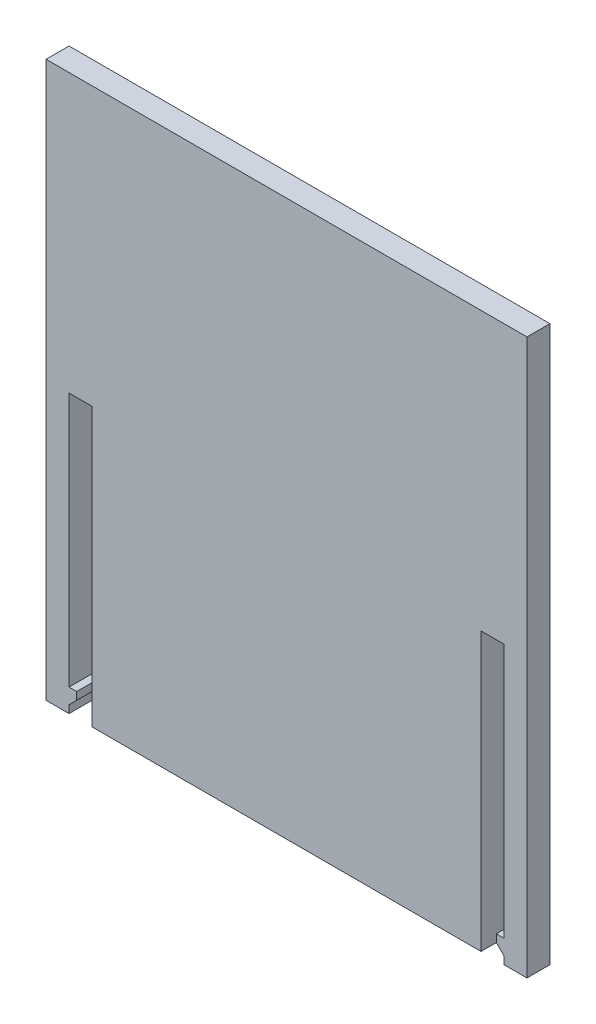
SolidWorks part; units mm, degrees
ref_plane "Front Plane" through (0, 0, 0) normal (0, 0, 1) x (1, 0, 0)
ref_plane "Top Plane" through (0, 0, 0) normal (0, 1, 0) x (1, 0, 0)
ref_plane "Right Plane" through (0, 0, 0) normal (1, 0, 0) x (0, 0, -1)
sketch "Sketch1" plane through (0, 0, 0) normal (0, 0, 1) x (1, 0, 0)
  line L37 (50.8, -10.8558) -> (50.8, -13.8558) construction
  line L38 (50.8, -13.8558) -> (53.8, -13.8558) construction
  line L39 (53.8, -13.8558) -> (53.8, -10.8558) construction
  line L41 (53.8, -10.8558) -> (50.8, -10.8558) construction
  line L42 (-3, -10.8558) -> (-3, -13.8558) construction
  line L43 (-3, -13.8558) -> (0, -13.8558) construction
  line L44 (0, -13.8558) -> (0, -10.8558) construction
  line L45 (0, -10.8558) -> (-3, -10.8558) construction
  line L46 (50.8, 58.6442) -> (50.8, 22.3942) construction
  line L47 (50.8, 22.3942) -> (53.8, 22.3942) construction
  line L48 (53.8, 22.3942) -> (53.8, 58.6442) construction
  line L49 (53.8, 58.6442) -> (50.8, 58.6442) construction
  line L50 (-3, 58.6442) -> (-3, 22.3942) construction
  line L51 (-3, 22.3942) -> (0, 22.3942) construction
  line L52 (0, 22.3942) -> (0, 58.6442) construction
  line L53 (0, 58.6442) -> (-3, 58.6442) construction
  line L54 (50.8, -10.8558) -> (50.8, -13.8558) construction
  line L55 (50.8, -13.8558) -> (53.8, -13.8558) construction
  line L56 (53.8, -13.8558) -> (53.8, -10.8558) construction
  line L57 (53.8, -10.8558) -> (50.8, -10.8558) construction
  line L58 (-3, -10.8558) -> (-3, -13.8558) construction
  line L59 (-3, -13.8558) -> (0, -13.8558) construction
  line L60 (0, -13.8558) -> (0, -10.8558) construction
  line L61 (0, -10.8558) -> (-3, -10.8558) construction
  line L62 (50.8, 58.6442) -> (50.8, 22.3942) construction
  line L63 (50.8, 22.3942) -> (53.8, 22.3942) construction
  line L64 (53.8, 22.3942) -> (53.8, 58.6442) construction
  line L65 (53.8, 58.6442) -> (50.8, 58.6442) construction
  line L66 (-3, 58.6442) -> (-3, 22.3942) construction
  line L67 (-3, 22.3942) -> (0, 22.3942) construction
  line L68 (0, 22.3942) -> (0, 58.6442) construction
  line L69 (0, 58.6442) -> (-3, 58.6442) construction
  line L71 (-6, 58.6442) -> (56.8, 58.6442)
  line L72 (-6, 58.6442) -> (-6, -13.8558)
  line L73 (-6, -13.8558) -> (56.8, -13.8558)
  line L74 (56.8, 58.6442) -> (56.8, -13.8558)
  line L75 (-6, 58.6442) -> (56.8, -13.8558) construction
  line L76 (-6, -13.8558) -> (56.8, 58.6442) construction
  line L77 (-3, 22.3942) -> (0, 22.3942)
  line L78 (-3, 22.3942) -> (-3, -10.8558)
  line L79 (-3, -10.8558) -> (0, -10.8558)
  line L80 (0, 22.3942) -> (0, -10.8558)
  line L81 (50.8, 22.3942) -> (53.8, 22.3942)
  line L82 (50.8, 22.3942) -> (50.8, -10.8558)
  line L83 (50.8, -10.8558) -> (53.8, -10.8558)
  line L84 (53.8, 22.3942) -> (53.8, -10.8558)
  point P2 (25.4, 22.3942)
  dimension "D1" = 3
  dimension "D2" = 3
extrude "Boss-Extrude1" add sketch "Sketch1" along normal blind 3
sketch "Sketch2" plane through (0, 0, 3) normal (0, 0, 1) x (1, 0, 0)
  line L0 (-6, -13.8558) -> (56.8, -13.8558) construction
  line L1 (-3, -10.8558) -> (0, -10.8558)
  line L2 (-3, -10.8558) -> (-3, -13.8558)
  line L3 (-3, -13.8558) -> (0, -13.8558)
  line L4 (0, -10.8558) -> (0, -13.8558)
  line L5 (-3, -10.8558) -> (-2, -10.8558)
  line L6 (-2, -10.8558) -> (-2, -11.8558)
  line L7 (-2, -11.8558) -> (-3, -12.8558)
  line M11 (-6, -13.8558) -> (56.8, -13.8558)
  line M17 (0, -10.8558) -> (-3, -10.8558)
  dimension "D1" = 1
  dimension "D2" = 1
  dimension "D3" = 135
extrude "Cut-Extrude1" cut sketch "Sketch2" against normal through all contours L6 L7 L2 L4 M11 M17 region at (-1.2889, -12.5002, 3)
ref_plane "Plane1" through (25.4, 0, 0) normal (-1, 0, 0) x (0, 0, 1)
mirror "Mirror1" about plane through (25.4, 0, 0) normal (-1, 0, 0) of "Cut-Extrude1"
equation "\"thick\"= 3mm"
equation "\"D1@Boss-Extrude1\"=\"thick\""
